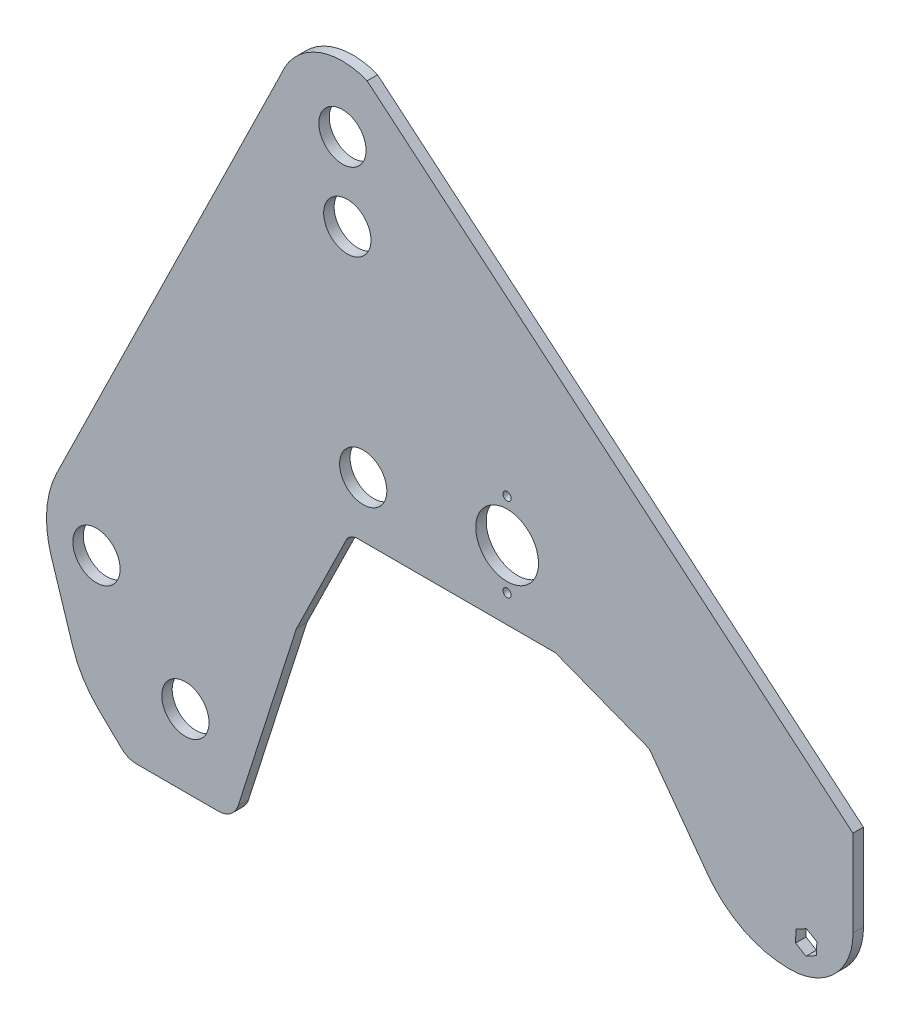
SolidWorks part; units mm, degrees
other "Markup1"
sketch "Sketch1" plane through (-441.7893, 331.8239, 6.35) normal (-0.0431, 0.0102, 0.999) x (0.9985, 0.0354, 0.0427)
ref_plane "Front Plane" through (0, 0, 0) normal (0, 0, 1) x (1, 0, 0)
ref_plane "Top Plane" through (0, 0, 0) normal (0, 1, 0) x (1, 0, 0)
ref_plane "Right Plane" through (0, 0, 0) normal (1, 0, 0) x (0, 0, -1)
sketch "Model" plane through (0, 0, 0) normal (0, 0, 1) x (1, 0, 0)
  line L0 (75.9485, 40.4103) -> (75.882, 92.9412)
  line L1 (-224.8827, 97.4651) -> (-104.7249, 97.4651)
  line L2 (-261.9342, 31.5683) -> (-231.7249, 93.1989)
  line L3 (-297.3401, -79.3119) -> (-261.9342, 31.5683)
  line L4 (-271.0052, 318.922) -> (-407.4479, 40.5627)
  line L5 (-410.7965, -4.7638) -> (-397.7579, -45.7118)
  line L6 (-104.7249, 97.4651) -> (-47.7354, 75.4359)
  line L7 (-381.9218, -71.1596) -> (-367.9389, -84.6036)
  line L8 (-47.7354, 75.4359) -> (-12.1905, 27.105)
  line L10 (36.9184, 2.262) -> (37.8485, 2.262)
  line L11 (75.882, 92.9412) -> (-219.0215, 341.0133)
  line L13 (53.9476, 24.8456) -> (47.6751, 28.6428)
  line L14 (47.6751, 28.6428) -> (41.2504, 25.1092)
  line L15 (41.2504, 25.1092) -> (41.0982, 17.7784)
  line L16 (41.0982, 17.7784) -> (47.3707, 13.9813)
  line L17 (47.3707, 13.9813) -> (53.7955, 17.5149)
  line L18 (53.7955, 17.5149) -> (53.9476, 24.8456)
  line L19 (-359.1367, -88.1487) -> (-309.4383, -88.1487)
  arc A2 (-219.0215, 341.0133) -> (-271.0052, 318.922) centre (-234, 304.0517) ccw
  circle A3 centre (-134.0441, 114.3) radius 2.4892
  arc A6 (-224.8827, 97.4651) -> (-231.7249, 93.1989) centre (-224.8827, 89.8451) ccw
  circle A9 centre (-329.3491, -44.474) radius 14.351
  circle A10 centre (-383.3239, 9.3141) radius 14.351
  circle A12 centre (-221.4052, 131.3317) radius 14.351
  circle A15 centre (-134.0441, 139.2879) radius 19.05
  circle A21 centre (-134.0441, 165.1) radius 2.4892
  circle A22 centre (-231.0489, 258.3317) radius 14.351
  circle A23 centre (-234, 304.0517) radius 14.351
  circle A24 centre (47.5229, 21.312) radius 6.35 construction
  arc A27 (75.9485, 40.4103) -> (37.8485, 2.262) centre (37.8485, 40.362) cw
  arc A28 (-12.1905, 27.105) -> (36.9184, 2.262) centre (36.9184, 63.222) ccw
  arc A29 (-410.7965, -4.7638) -> (-407.4479, 40.5627) centre (-352.7101, 13.732) cw
  arc A30 (-397.7579, -45.7118) -> (-381.9218, -71.1596) centre (-339.6715, -27.216) ccw
  arc A31 (-309.4383, -88.1487) -> (-297.3401, -79.3119) centre (-309.4383, -75.4487) ccw
  arc A32 (-359.1367, -88.1487) -> (-367.9389, -84.6036) centre (-359.1367, -75.4487) cw
  point P10 (0, 0)
  point P19 (-328.2352, -44.3731)
  dimension "D2" = 127
  dimension "D3" = 38.1
  dimension "D4" = 60.96
  dimension "D5" = 7.62
  dimension "D1" = 127
  dimension "D7" = 12.7
  dimension "D8" = 152.4
  dimension "D11" = 60.96
  dimension "D12" = 60.96
  dimension "D21" = 109.4608
  dimension "D13" = 12.7
  dimension "D16" = 12.7
  dimension "D9" = 19.05
  dimension "D10" = 76.2
  dimension "D14" = 45.72
  dimension "D15" = 33.8667
  dimension "D17" = 291.886
  dimension "D18" = 206.2996
  dimension "D19" = 41.8228
  dimension "D20" = 134.62
  dimension "D22" = 43.6748
extrude "Boss-Extrude1" add sketch "Model" along normal blind 6.35 contours L5 L7 L3 L2 L1 L6 L8 L10 L0 L11 A2 L4 A23 A22 A21 A3 A9 A10 A12 A15 region at (-200.057, 127.9176, 0)
